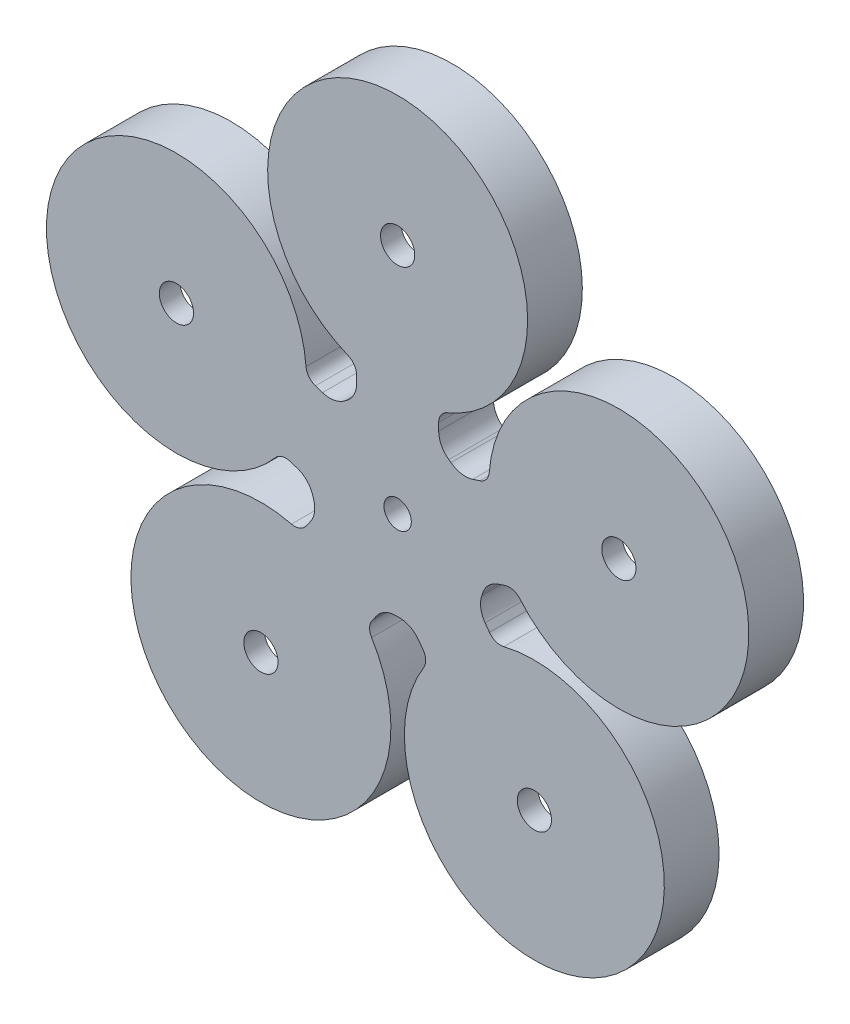
SolidWorks part; units mm, degrees
ref_plane "Front Plane" through (0, 0, 0) normal (0, 0, 1) x (1, 0, 0)
ref_plane "Top Plane" through (0, 0, 0) normal (0, 1, 0) x (1, 0, 0)
ref_plane "Right Plane" through (0, 0, 0) normal (1, 0, 0) x (0, 0, -1)
sketch "Sketch1" plane through (0, 0, 0) normal (0, 0, 1) x (1, 0, 0)
  line L0 (8.1454, 5.801) -> (16.4618, 8.5032)
  line L1 (-3, 9.5394) -> (-3, 18.2838)
  line L2 (18.3159, 2.7968) -> (9.9996, 0.0947)
  line L3 (3, 18.2838) -> (3, 9.5394)
  line L4 (8.0342, -5.9542) -> (13.174, -13.0285)
  line L5 (8.3199, -16.5552) -> (3.1801, -9.4809)
  line L6 (-3.1801, -9.4809) -> (-8.3199, -16.5552)
  line L7 (-13.174, -13.0285) -> (-8.0342, -5.9542)
  line L8 (-9.9996, 0.0947) -> (-18.3159, 2.7968)
  line L9 (-16.4618, 8.5032) -> (-8.1454, 5.801)
  line L10 (-3, 9.5394) -> (-3, 0) construction
  line L11 (-3, 0) -> (0, 0) construction
  line L12 (0, 0) -> (3, 0) construction
  line L13 (3, 0) -> (3, 9.5394) construction
  circle A0 centre (0, 0) radius 50 construction
  arc A1 (-3, 9.5394) -> (-8.1454, 5.801) centre (0, 0) ccw
  arc A2 (3, 18.2838) -> (-3, 18.2838) centre (0, 34) ccw
  circle A3 centre (0, 34) radius 13
  circle A4 centre (32.3359, 10.5066) radius 13
  arc A5 (18.3159, 2.7968) -> (16.4618, 8.5032) centre (32.3359, 10.5066) ccw
  circle A6 centre (19.9847, -27.5066) radius 13
  arc A7 (8.3199, -16.5552) -> (13.174, -13.0285) centre (19.9847, -27.5066) ccw
  circle A8 centre (-19.9847, -27.5066) radius 13
  arc A9 (-13.174, -13.0285) -> (-8.3199, -16.5552) centre (-19.9847, -27.5066) ccw
  circle A10 centre (-32.3359, 10.5066) radius 13
  arc A11 (-16.4618, 8.5032) -> (-18.3159, 2.7968) centre (-32.3359, 10.5066) ccw
  arc A12 (-9.9996, 0.0947) -> (-8.0342, -5.9542) centre (0, 0) ccw
  arc A13 (8.1454, 5.801) -> (3, 9.5394) centre (0, 0) ccw
  arc A14 (8.0342, -5.9542) -> (9.9996, 0.0947) centre (0, 0) ccw
  arc A15 (-3.1801, -9.4809) -> (3.1801, -9.4809) centre (0, 0) ccw
  point P35 (0, 0)
  dimension "D1" = 100
  dimension "D2" = 20
  dimension "D3" = 32
  dimension "D4" = 26
  dimension "D5" = 6
  dimension "D6" = 5
extrude "Boss-Extrude1" add sketch "Sketch1" along normal blind 120
sketch "Sketch2" plane through (0, 0, 0) normal (0, 0, -1) x (-1, 0, 0)
  circle A0 centre (0, 0) radius 55
  dimension "D1" = 110
extrude "Boss-Extrude2" [suppressed] add sketch "Sketch2" along normal blind 15
fillet "Fillet1" [suppressed] radius 5
fillet "Fillet2" [suppressed] radius 5
fillet "Fillet3" [suppressed] radius 6.5
sketch "Sketch3" [suppressed] plane through (0, 0, 0) normal (0, 1, 0) x (1, 0, 0)
  line L0 (-44, 15) -> (-44, 10)
  line L1 (55, 15) -> (-55, 15) construction
  line L2 (-44, 10) -> (-47, 10)
  line L3 (-47, 10) -> (-47, 5)
  line L4 (-47, 5) -> (-37, 5)
  line L5 (-37, 5) -> (-37, 10)
  line L6 (-37, 10) -> (-40, 10)
  line L7 (-40, 10) -> (-40, 15)
  line L8 (-40, 15) -> (-44, 15)
  line L9 (-55, 15) -> (-55, 0) construction
  dimension "D1" = 4
  dimension "D2" = 10
  dimension "D3" = 8
  dimension "D4" = 5
  dimension "D5" = 5
revolve "Cut-Revolve1" [suppressed] cut sketch "Sketch3" angle 360
sketch "Sketch4" [suppressed] plane through (0, 0, 0) normal (0, 0, 1) x (1, 0, 0)
  line L0 (-19.9596, 27.472) -> (-12.3763, 17.0345) construction
  circle A0 centre (0, 0) radius 42 construction
  arc A1 (0, 55) -> (-52.3081, 16.9959) centre (0, 0) ccw construction
  circle A2 centre (-24.687, 33.9787) radius 5
  dimension "D1" = 13
extrude "Cut-Extrude1" [suppressed] cut sketch "Sketch4" against normal blind 5 and the other way through all
sketch "Sketch5" [suppressed] plane through (0, 0, 0) normal (0, 0, 1) x (1, 0, 0)
  circle A0 centre (0, 34) radius 2.5
  circle A1 centre (32.3359, 10.5066) radius 2.5
  circle A2 centre (19.9847, -27.5066) radius 2.5
  circle A3 centre (-19.9847, -27.5066) radius 2.5
  circle A4 centre (-32.3359, 10.5066) radius 2.5
  point P13 (0, 0)
  dimension "D1" = 5
  dimension "D2" = 5
extrude "Cut-Extrude2" [suppressed] cut sketch "Sketch5" against normal through all
extrude "Cut-Extrude3" cut sketch "Sketch2<2>" against normal blind 110 and the other way blind 53
sketch "Sketch2<2>" plane through (0, 0, 0) normal (0, 0, -1) x (-1, 0, 0) same geometry as "Sketch2"
sketch "Sketch6" plane through (0, 0, 110) normal (0, 0, -1) x (-1, 0, 0)
  line L20 (-15.7238, -1.1998) -> (-14.6846, -1.5375)
  line L21 (-12.7838, -7.3875) -> (-13.4261, -8.2716)
  line L22 (-3.7179, -15.325) -> (-3.0756, -14.4409)
  line L23 (3.0756, -14.4409) -> (3.7179, -15.325)
  line L24 (13.4261, -8.2716) -> (12.7838, -7.3875)
  line L25 (14.6846, -1.5375) -> (15.7238, -1.1998)
  line L26 (12.0156, 10.2129) -> (10.9764, 9.8752)
  line L27 (6, 13.4907) -> (6, 14.5835)
  line L28 (-6, 14.5835) -> (-6, 13.4907)
  line L29 (-10.9764, 9.8752) -> (-12.0156, 10.2129)
  arc A70 (-13.3917, 11.9618) -> (-17.8651, -1.8059) centre (-32.3359, 10.5066) ccw
  arc A71 (-15.7238, -1.1998) -> (-17.8651, -1.8059) centre (-16.3419, -3.1019) ccw
  arc A72 (-12.4218, -3.834) -> (-14.6846, -1.5375) centre (-15.7661, -4.8662) ccw
  arc A73 (-12.4218, -3.834) -> (-12.303, -4.1996) centre (0, 0) ccw
  arc A74 (-12.7838, -7.3875) -> (-12.303, -4.1996) centre (-15.6153, -5.3303) ccw
  arc A75 (-15.5146, -9.0399) -> (-13.4261, -8.2716) centre (-15.0441, -7.096) ccw
  arc A76 (-15.5146, -9.0399) -> (-3.8032, -17.5488) centre (-19.9847, -27.5066) ccw
  arc A77 (-3.7179, -15.325) -> (-3.8032, -17.5488) centre (-2.0998, -16.5006) ccw
  arc A78 (-0.1922, -12.9986) -> (-3.0756, -14.4409) centre (-0.244, -16.4982) ccw
  arc A79 (-0.1922, -12.9986) -> (0.1922, -12.9986) centre (0, 0) ccw
  arc A80 (3.0756, -14.4409) -> (0.1922, -12.9986) centre (0.244, -16.4982) ccw
  arc A81 (3.8032, -17.5488) -> (3.7179, -15.325) centre (2.0998, -16.5006) ccw
  arc A82 (3.8032, -17.5488) -> (15.5146, -9.0399) centre (19.9847, -27.5066) ccw
  arc A83 (13.4261, -8.2716) -> (15.5146, -9.0399) centre (15.0441, -7.096) ccw
  arc A84 (12.303, -4.1996) -> (12.7838, -7.3875) centre (15.6153, -5.3303) ccw
  arc A85 (12.303, -4.1996) -> (12.4218, -3.834) centre (0, 0) ccw
  arc A86 (14.6846, -1.5375) -> (12.4218, -3.834) centre (15.7661, -4.8662) ccw
  arc A87 (17.8651, -1.8059) -> (15.7238, -1.1998) centre (16.3419, -3.1019) ccw
  arc A88 (17.8651, -1.8059) -> (13.3917, 11.9618) centre (32.3359, 10.5066) ccw
  arc A89 (12.0156, 10.2129) -> (13.3917, 11.9618) centre (11.3976, 12.115) ccw
  arc A90 (7.7959, 10.4031) -> (10.9764, 9.8752) centre (9.8948, 13.2039) ccw
  arc A91 (7.7959, 10.4031) -> (7.4848, 10.6291) centre (0, 0) ccw
  arc A92 (6, 13.4907) -> (7.4848, 10.6291) centre (9.5, 13.4907) ccw
  arc A93 (7.2381, 16.4327) -> (6, 14.5835) centre (8, 14.5835) ccw
  arc A94 (7.2381, 16.4327) -> (-7.2381, 16.4327) centre (0, 34) ccw
  arc A95 (-6, 14.5835) -> (-7.2381, 16.4327) centre (-8, 14.5835) ccw
  arc A96 (-7.4848, 10.6291) -> (-6, 13.4907) centre (-9.5, 13.4907) ccw
  arc A97 (-7.4848, 10.6291) -> (-7.7959, 10.4031) centre (0, 0) ccw
  arc A98 (-10.9764, 9.8752) -> (-7.7959, 10.4031) centre (-9.8948, 13.2039) ccw
  arc A99 (-13.3917, 11.9618) -> (-12.0156, 10.2129) centre (-11.3976, 12.115) ccw
extrude "Boss-Extrude3" add sketch "Sketch6" along normal blind 3
extrude "Cut-Extrude4" cut sketch "Sketch6<2>" against normal through all
sketch "Sketch6<2>" plane through (0, 0, 110) normal (0, 0, -1) x (-1, 0, 0) same geometry as "Sketch6"
sketch "Sketch7" plane through (0, 0, 107) normal (0, 0, -1) x (-1, 0, 0)
  line L0 (-6.1449, -13.5617) -> (-5.5026, -12.6776)
  line L1 (5.5026, -12.6776) -> (6.1449, -13.5617)
  line L2 (10.999, -10.035) -> (10.3567, -9.1509)
  line L3 (13.7575, 1.3157) -> (14.7968, 1.6534)
  line L4 (12.9427, 7.3597) -> (11.9034, 7.022)
  line L5 (3, 13.4907) -> (3, 14.5835)
  line L6 (-3, 14.5835) -> (-3, 13.4907)
  line L7 (-11.9034, 7.022) -> (-12.9427, 7.3597)
  line L8 (-14.7968, 1.6534) -> (-13.7575, 1.3157)
  line L9 (-10.3567, -9.1509) -> (-10.999, -10.035)
  line L10 (-10.9764, 9.8752) -> (-12.0156, 10.2129)
  line L11 (-6, 14.5835) -> (-6, 13.4907)
  line L12 (6, 13.4907) -> (6, 14.5835)
  line L13 (12.0156, 10.2129) -> (10.9764, 9.8752)
  line L14 (14.6846, -1.5375) -> (15.7238, -1.1998)
  line L15 (13.4261, -8.2716) -> (12.7838, -7.3875)
  line L16 (3.0756, -14.4409) -> (3.7179, -15.325)
  line L17 (-3.7179, -15.325) -> (-3.0756, -14.4409)
  line L18 (-12.7838, -7.3875) -> (-13.4261, -8.2716)
  line L19 (-15.7238, -1.1998) -> (-14.6846, -1.5375)
  line L20 (-10.9764, 9.8752) -> (-12.0156, 10.2129)
  line L21 (-6, 14.5835) -> (-6, 13.4907)
  line L22 (6, 13.4907) -> (6, 14.5835)
  line L23 (12.0156, 10.2129) -> (10.9764, 9.8752)
  line L24 (14.6846, -1.5375) -> (15.7238, -1.1998)
  line L25 (13.4261, -8.2716) -> (12.7838, -7.3875)
  line L26 (3.0756, -14.4409) -> (3.7179, -15.325)
  line L27 (-3.7179, -15.325) -> (-3.0756, -14.4409)
  line L28 (-12.7838, -7.3875) -> (-13.4261, -8.2716)
  line L29 (-15.7238, -1.1998) -> (-14.6846, -1.5375)
  arc A0 (-16.2204, -11.9557) -> (-6.3581, -19.1211) centre (-19.9847, -27.5066) ccw
  arc A1 (-6.1449, -13.5617) -> (-6.3581, -19.1211) centre (-2.0998, -16.5006) ccw
  arc A2 (-0.1479, -9.9989) -> (-5.5026, -12.6776) centre (-0.244, -16.4982) ccw
  arc A3 (-0.1479, -9.9989) -> (0.1479, -9.9989) centre (0, 0) ccw
  arc A4 (5.5026, -12.6776) -> (0.1479, -9.9989) centre (0.244, -16.4982) ccw
  arc A5 (6.3581, -19.1211) -> (6.1449, -13.5617) centre (2.0998, -16.5006) ccw
  arc A6 (6.3581, -19.1211) -> (16.2204, -11.9557) centre (19.9847, -27.5066) ccw
  arc A7 (10.999, -10.035) -> (16.2204, -11.9557) centre (15.0441, -7.096) ccw
  arc A8 (9.4638, -3.2305) -> (10.3567, -9.1509) centre (15.6153, -5.3303) ccw
  arc A9 (9.4638, -3.2305) -> (9.5552, -2.9492) centre (0, 0) ccw
  arc A10 (13.7575, 1.3157) -> (9.5552, -2.9492) centre (15.7661, -4.8662) ccw
  arc A11 (20.15, 0.1382) -> (14.7968, 1.6534) centre (16.3419, -3.1019) ccw
  arc A12 (20.15, 0.1382) -> (16.3829, 11.732) centre (32.3359, 10.5066) ccw
  arc A13 (12.9427, 7.3597) -> (16.3829, 11.732) centre (11.3976, 12.115) ccw
  arc A14 (5.9968, 8.0024) -> (11.9034, 7.022) centre (9.8948, 13.2039) ccw
  arc A15 (5.9968, 8.0024) -> (5.7576, 8.1762) centre (0, 0) ccw
  arc A16 (3, 13.4907) -> (5.7576, 8.1762) centre (9.5, 13.4907) ccw
  arc A17 (6.0952, 19.2065) -> (3, 14.5835) centre (8, 14.5835) ccw
  arc A18 (6.0952, 19.2065) -> (-6.0952, 19.2065) centre (0, 34) ccw
  arc A19 (-3, 14.5835) -> (-6.0952, 19.2065) centre (-8, 14.5835) ccw
  arc A20 (-5.7576, 8.1762) -> (-3, 13.4907) centre (-9.5, 13.4907) ccw
  arc A21 (-5.7576, 8.1762) -> (-5.9968, 8.0024) centre (0, 0) ccw
  arc A22 (-11.9034, 7.022) -> (-5.9968, 8.0024) centre (-9.8948, 13.2039) ccw
  arc A23 (-16.3829, 11.732) -> (-12.9427, 7.3597) centre (-11.3976, 12.115) ccw
  arc A24 (-16.3829, 11.732) -> (-20.15, 0.1382) centre (-32.3359, 10.5066) ccw
  arc A25 (-14.7968, 1.6534) -> (-20.15, 0.1382) centre (-16.3419, -3.1019) ccw
  arc A26 (-9.5552, -2.9492) -> (-13.7575, 1.3157) centre (-15.7661, -4.8662) ccw
  arc A27 (-9.5552, -2.9492) -> (-9.4638, -3.2305) centre (0, 0) ccw
  arc A28 (-10.3567, -9.1509) -> (-9.4638, -3.2305) centre (-15.6153, -5.3303) ccw
  arc A29 (-16.2204, -11.9557) -> (-10.999, -10.035) centre (-15.0441, -7.096) ccw
  arc A30 (-10.9764, 9.8752) -> (-7.7959, 10.4031) centre (-9.8948, 13.2039) ccw
  arc A31 (-7.4848, 10.6291) -> (-7.7959, 10.4031) centre (0, 0) ccw
  arc A32 (-7.4848, 10.6291) -> (-6, 13.4907) centre (-9.5, 13.4907) ccw
  arc A33 (-6, 14.5835) -> (-7.2381, 16.4327) centre (-8, 14.5835) ccw
  arc A34 (7.2381, 16.4327) -> (-7.2381, 16.4327) centre (0, 34) ccw
  arc A35 (7.2381, 16.4327) -> (6, 14.5835) centre (8, 14.5835) ccw
  arc A36 (6, 13.4907) -> (7.4848, 10.6291) centre (9.5, 13.4907) ccw
  arc A37 (7.7959, 10.4031) -> (7.4848, 10.6291) centre (0, 0) ccw
  arc A38 (7.7959, 10.4031) -> (10.9764, 9.8752) centre (9.8948, 13.2039) ccw
  arc A39 (12.0156, 10.2129) -> (13.3917, 11.9618) centre (11.3976, 12.115) ccw
  arc A40 (17.8651, -1.8059) -> (13.3917, 11.9618) centre (32.3359, 10.5066) ccw
  arc A41 (17.8651, -1.8059) -> (15.7238, -1.1998) centre (16.3419, -3.1019) ccw
  arc A42 (14.6846, -1.5375) -> (12.4218, -3.834) centre (15.7661, -4.8662) ccw
  arc A43 (12.303, -4.1996) -> (12.4218, -3.834) centre (0, 0) ccw
  arc A44 (12.303, -4.1996) -> (12.7838, -7.3875) centre (15.6153, -5.3303) ccw
  arc A45 (13.4261, -8.2716) -> (15.5146, -9.0399) centre (15.0441, -7.096) ccw
  arc A46 (3.8032, -17.5488) -> (15.5146, -9.0399) centre (19.9847, -27.5066) ccw
  arc A47 (3.8032, -17.5488) -> (3.7179, -15.325) centre (2.0998, -16.5006) ccw
  arc A48 (3.0756, -14.4409) -> (0.1922, -12.9986) centre (0.244, -16.4982) ccw
  arc A49 (-0.1922, -12.9986) -> (0.1922, -12.9986) centre (0, 0) ccw
  arc A50 (-0.1922, -12.9986) -> (-3.0756, -14.4409) centre (-0.244, -16.4982) ccw
  arc A51 (-3.7179, -15.325) -> (-3.8032, -17.5488) centre (-2.0998, -16.5006) ccw
  arc A52 (-15.5146, -9.0399) -> (-3.8032, -17.5488) centre (-19.9847, -27.5066) ccw
  arc A53 (-15.5146, -9.0399) -> (-13.4261, -8.2716) centre (-15.0441, -7.096) ccw
  arc A54 (-12.7838, -7.3875) -> (-12.303, -4.1996) centre (-15.6153, -5.3303) ccw
  arc A55 (-12.4218, -3.834) -> (-12.303, -4.1996) centre (0, 0) ccw
  arc A56 (-12.4218, -3.834) -> (-14.6846, -1.5375) centre (-15.7661, -4.8662) ccw
  arc A57 (-15.7238, -1.1998) -> (-17.8651, -1.8059) centre (-16.3419, -3.1019) ccw
  arc A58 (-13.3917, 11.9618) -> (-17.8651, -1.8059) centre (-32.3359, 10.5066) ccw
  arc A59 (-13.3917, 11.9618) -> (-12.0156, 10.2129) centre (-11.3976, 12.115) ccw
  arc A60 (-10.9764, 9.8752) -> (-7.7959, 10.4031) centre (-9.8948, 13.2039) ccw
  arc A61 (-7.4848, 10.6291) -> (-7.7959, 10.4031) centre (0, 0) ccw
  arc A62 (-7.4848, 10.6291) -> (-6, 13.4907) centre (-9.5, 13.4907) ccw
  arc A63 (-6, 14.5835) -> (-7.2381, 16.4327) centre (-8, 14.5835) ccw
  arc A64 (7.2381, 16.4327) -> (-7.2381, 16.4327) centre (0, 34) ccw
  arc A65 (7.2381, 16.4327) -> (6, 14.5835) centre (8, 14.5835) ccw
  arc A66 (6, 13.4907) -> (7.4848, 10.6291) centre (9.5, 13.4907) ccw
  arc A67 (7.7959, 10.4031) -> (7.4848, 10.6291) centre (0, 0) ccw
  arc A68 (7.7959, 10.4031) -> (10.9764, 9.8752) centre (9.8948, 13.2039) ccw
  arc A69 (12.0156, 10.2129) -> (13.3917, 11.9618) centre (11.3976, 12.115) ccw
  arc A70 (17.8651, -1.8059) -> (13.3917, 11.9618) centre (32.3359, 10.5066) ccw
  arc A71 (17.8651, -1.8059) -> (15.7238, -1.1998) centre (16.3419, -3.1019) ccw
  arc A72 (14.6846, -1.5375) -> (12.4218, -3.834) centre (15.7661, -4.8662) ccw
  arc A73 (12.303, -4.1996) -> (12.4218, -3.834) centre (0, 0) ccw
  arc A74 (12.303, -4.1996) -> (12.7838, -7.3875) centre (15.6153, -5.3303) ccw
  arc A75 (13.4261, -8.2716) -> (15.5146, -9.0399) centre (15.0441, -7.096) ccw
  arc A76 (3.8032, -17.5488) -> (15.5146, -9.0399) centre (19.9847, -27.5066) ccw
  arc A77 (3.8032, -17.5488) -> (3.7179, -15.325) centre (2.0998, -16.5006) ccw
  arc A78 (3.0756, -14.4409) -> (0.1922, -12.9986) centre (0.244, -16.4982) ccw
  arc A79 (-0.1922, -12.9986) -> (0.1922, -12.9986) centre (0, 0) ccw
  arc A80 (-0.1922, -12.9986) -> (-3.0756, -14.4409) centre (-0.244, -16.4982) ccw
  arc A81 (-3.7179, -15.325) -> (-3.8032, -17.5488) centre (-2.0998, -16.5006) ccw
  arc A82 (-15.5146, -9.0399) -> (-3.8032, -17.5488) centre (-19.9847, -27.5066) ccw
  arc A83 (-15.5146, -9.0399) -> (-13.4261, -8.2716) centre (-15.0441, -7.096) ccw
  arc A84 (-12.7838, -7.3875) -> (-12.303, -4.1996) centre (-15.6153, -5.3303) ccw
  arc A85 (-12.4218, -3.834) -> (-12.303, -4.1996) centre (0, 0) ccw
  arc A86 (-12.4218, -3.834) -> (-14.6846, -1.5375) centre (-15.7661, -4.8662) ccw
  arc A87 (-15.7238, -1.1998) -> (-17.8651, -1.8059) centre (-16.3419, -3.1019) ccw
  arc A88 (-13.3917, 11.9618) -> (-17.8651, -1.8059) centre (-32.3359, 10.5066) ccw
  arc A89 (-13.3917, 11.9618) -> (-12.0156, 10.2129) centre (-11.3976, 12.115) ccw
  dimension "D1" = 0
  dimension "D2" = 3
extrude "Boss-Extrude4" add sketch "Sketch7" along normal blind 5
sketch "Sketch8" plane through (0, 0, 110) normal (0, 0, 1) x (1, 0, 0)
  circle A0 centre (0, 0) radius 2
  circle A1 centre (0, 34) radius 2.5
  circle A2 centre (32.3359, 10.5066) radius 2.5
  circle A3 centre (19.9847, -27.5066) radius 2.5
  circle A4 centre (-19.9847, -27.5066) radius 2.5
  circle A5 centre (-32.3359, 10.5066) radius 2.5
  point P16 (0, 0)
  dimension "D1" = 4
  dimension "D2" = 5
  dimension "D3" = 5
extrude "Cut-Extrude5" cut sketch "Sketch8" against normal through all both and the other way through all
